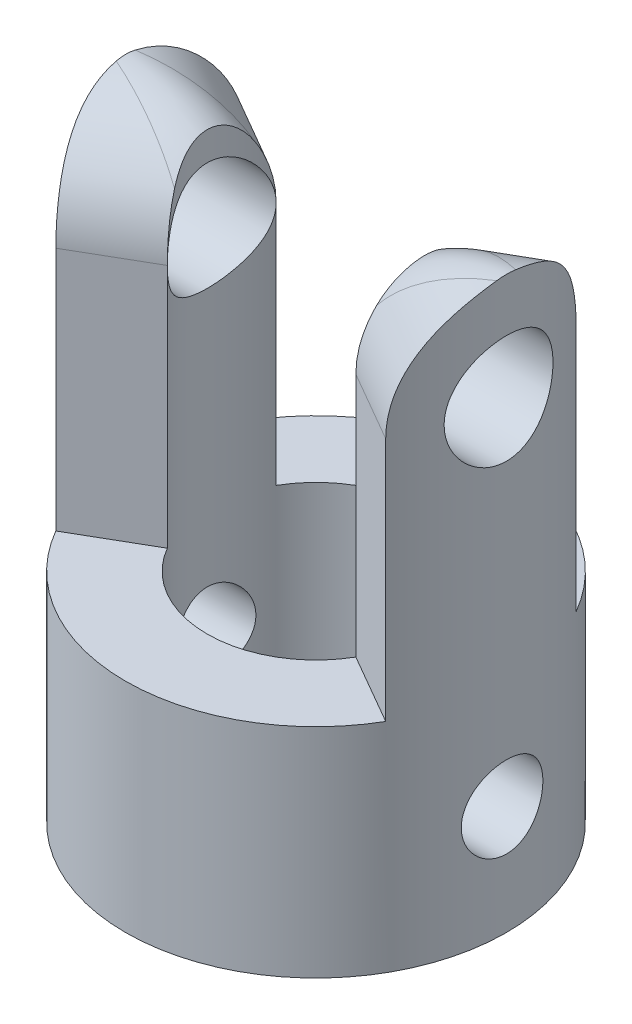
SolidWorks part; units mm, degrees
ref_plane "前视基准面" through (0, 0, 0) normal (0, 0, 1) x (1, 0, 0)
ref_plane "上视基准面" through (0, 0, 0) normal (0, 1, 0) x (1, 0, 0)
ref_plane "右视基准面" through (0, 0, 0) normal (1, 0, 0) x (0, 0, -1)
other "Configuration Table"
sketch "草图1" plane through (0, 0, 0) normal (0, 1, 0) x (1, 0, 0)
  circle A0 centre (0, 0) radius 7
  circle A1 centre (0, 0) radius 4
  dimension "D1" = 14
  dimension "D2" = 8
extrude "凸台-拉伸2" add sketch "草图1" along normal blind 21
sketch "草图2" plane through (0, 21, 0) normal (0, 1, 0) x (1, 0, 0)
  line L0 (0, 7) -> (0, -7) construction
  line L1 (-7, 0) -> (7, 0) construction
  line L2 (0, 0) -> (-6.0622, 3.5) construction
  line L3 (0, 0) -> (-6.0622, -3.5) construction
  line L4 (0, 0) -> (6.0622, -3.5) construction
  line L5 (0, 0) -> (6.0622, 3.5) construction
  line L6 (-6.0622, 3.5) -> (6.0622, -3.5)
  line L7 (-6.0622, -3.5) -> (6.0622, 3.5)
  circle A0 centre (0, 0) radius 7 construction
  arc A1 (-6.0622, 3.5) -> (6.0622, 3.5) centre (0, 0) cw
  arc A2 (-6.0622, -3.5) -> (6.0622, -3.5) centre (0, 0) ccw
  circle A3 centre (0, 0) radius 4
  circle M5 centre (0, 0) radius 7
  circle M6 centre (0, 0) radius 4
  dimension "D2" = 8
  dimension "D1" = 30
extrude "切除-拉伸1" cut sketch "草图2" against normal blind 13 contours L7 L6 M5 M6 | L7 L6 M6 M5
fillet "圆角1" radius 4 8 edges at (-4, 21, 0) (-7, 21, 0) (-4.7631, 21, 2.75) (4.7631, 21, 2.75) (4.7631, 21, -2.75) (-4.7631, 21, -2.75) (7, 21, 0) (4, 21, 0)
fillet "圆角3" radius 2 2 edges at (-5.4496, 20.7913, 0) (5.4496, 20.7913, 0)
sketch "草图3" plane through (0, 0, 0) normal (1, 0, 0) x (0, 0, -1)
  line L0 (0, 0) -> (0, 17) construction
  line L1 (-7, 0) -> (7, 0) construction
  circle A0 centre (0, 17) radius 2
  dimension "D1" = 4
  dimension "D2" = 17
extrude "切除-拉伸2" cut sketch "草图3" against normal through all and the other way through all contours A0
sketch "草图5" plane through (0, 0, 0) normal (1, 0, 0) x (0, 0, -1)
  line L0 (-7, 0) -> (7, 0) construction
  line L1 (0, 0) -> (0, 4) construction
  circle A0 centre (0, 4) radius 1.5
  dimension "D1" = 3
  dimension "D2" = 4
extrude "切除-拉伸3" cut sketch "草图5" against normal through all and the other way through all
